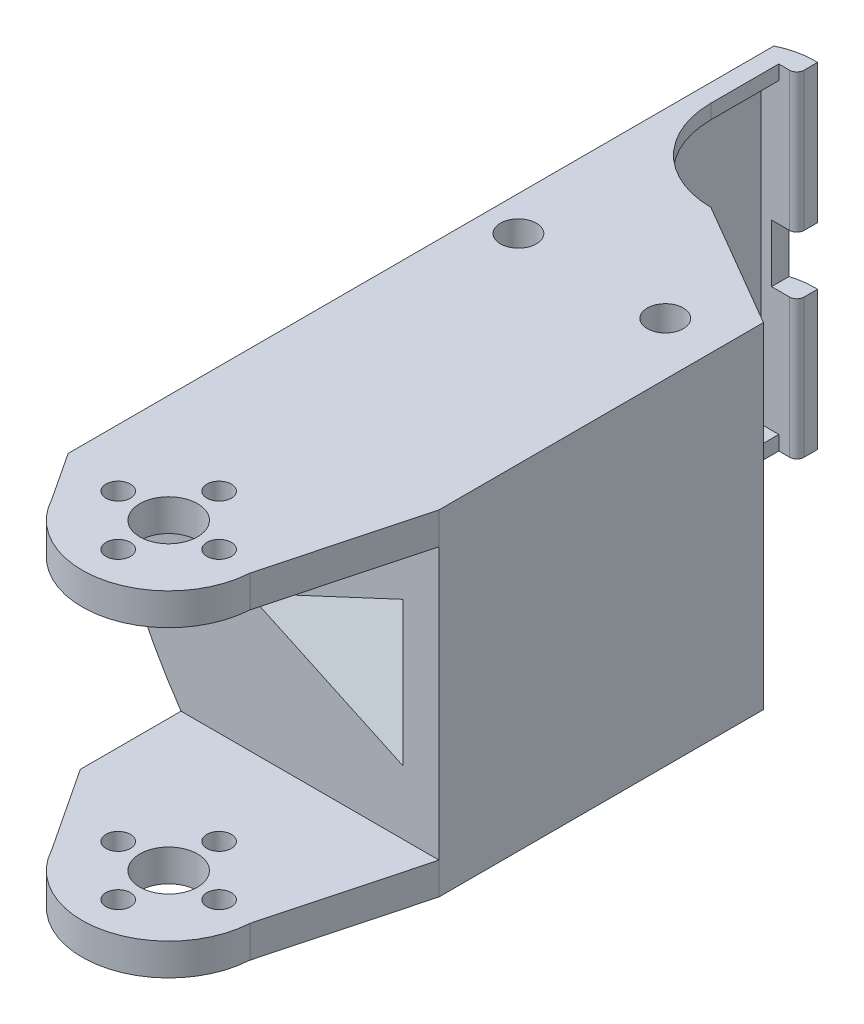
SolidWorks part; units mm, degrees
ref_plane "Front Plane" through (0, 0, 0) normal (0, 0, 1) x (1, 0, 0)
ref_plane "Top Plane" through (0, 0, 0) normal (0, 1, 0) x (1, 0, 0)
ref_plane "Right Plane" through (0, 0, 0) normal (1, 0, 0) x (0, 0, -1)
sketch "Sketch2" plane through (0, 0, 0) normal (0, 1, 0) x (1, 0, 0)
  line L0 (17.5, 0) -> (17.5, 37.7)
  line L1 (-15, 2.5) -> (15, 2.5)
  line L2 (-15, 2.5) -> (-15, 37.7)
  line L4 (15, 2.5) -> (15, 37.7)
  line L5 (17.5, 37.7) -> (15, 37.7)
  line L7 (-17.5, 37.7) -> (-17.5, 0)
  line L8 (-17.5, 0) -> (17.5, 0)
  line L10 (-17.5, 37.7) -> (-15, 37.7)
  point P4 (0, 2.5)
  point P12 (0, 0)
  dimension "D1" = 2.5
  dimension "D2" = 2.5
  dimension "D3" = 37.7
  dimension "D4" = 30
  dimension "D5" = 15
extrude "Boss-Extrude1" add sketch "Sketch2" along normal blind 32.5
sketch "Sketch4" plane through (0, 0, 0) normal (0, -1, 0) x (1, 0, 0)
  line L0 (-17.5, 0) -> (-17.5, -7.4438)
  line L8 (17.5, -7.4438) -> (17.5, 0)
  line L9 (17.5, 0) -> (-17.5, 0)
  line L10 (17.5, 0) -> (17.5, -37.7) construction
  line L13 (-17.5, -7.4438) -> (-17.5, -37.7)
  line L23 (-17.5, -37.7) -> (-15, -37.7)
  line L34 (-15, -37.7) -> (-15, -7.5)
  line L35 (-15, -2.5) -> (-15, -37.7) construction
  line L36 (-15, -7.5) -> (15, -7.5)
  line L37 (15, -37.7) -> (15, -2.5) construction
  line L38 (15, -7.5) -> (15, -37.7)
  line L39 (15, -37.7) -> (17.5, -37.7)
  line L40 (17.5, -37.7) -> (17.5, -7.4438)
  circle A2 centre (-10.1889, -4.95) radius 1.05
  circle A5 centre (10.1889, -4.95) radius 1.05
  dimension "D5" = 2.1
  dimension "D1" = 7.5
  dimension "D6" = 7.3111
  dimension "D7" = 4.95
  dimension "D8" = 7.3111
extrude "Boss-Extrude2" add sketch "Sketch4" along normal blind 2
sketch "Sketch7" plane through (0, -2, 0) normal (0, -1, 0) x (1, 0, 0)
  line L0 (-17.5, 0) -> (-17.5, -37.7)
  line L1 (-17.5, -37.7) -> (-15, -37.7)
  line L2 (-17.5, 0) -> (17.5, 0)
  line L4 (17.5, 0) -> (17.5, -37.7)
  line L5 (17.5, -37.7) -> (15, -37.7)
  line L6 (15, -37.7) -> (15, -7.5)
  line L7 (15, -7.5) -> (-15, -7.5)
  line L8 (-15, -7.5) -> (-15, -37.7)
  circle A2 centre (-10.1889, -4.95) radius 2.495
  circle A3 centre (10.1889, -4.95) radius 2.495
  dimension "D1" = 4.99
extrude "Wire spacing2" add sketch "Sketch7" along normal blind 3
sketch "Sketch8" plane through (0, -5, 0) normal (0, -1, 0) x (1, 0, 0)
  line L0 (-17.5, 0) -> (-17.5, -37.7)
  line L1 (-17.5, -37.7) -> (17.5, -37.7)
  line L2 (17.5, -37.7) -> (17.5, 0) construction
  line L3 (15, -37.7) -> (17.5, -37.7) construction
  line L4 (-17.5, 0) -> (17.5, 0)
  line L6 (17.5, 0) -> (17.5, -37.7)
  circle A0 centre (-10.1889, -4.95) radius 2.495
  circle A1 centre (10.1889, -4.95) radius 2.495
  circle A2 centre (10.1889, -4.95) radius 2.495 construction
  circle A3 centre (-10.1889, -4.95) radius 2.495 construction
extrude "Boss-Extrude6" add sketch "Sketch8" along normal blind 2
sketch "Sketch5" plane through (0, 32.5, 0) normal (0, 1, 0) x (1, 0, 0)
  line L0 (-7.439, 10) -> (-7.439, 2.5)
  line L9 (15, 2.5) -> (-15, 2.5) construction
  line L11 (-10.1889, 12) -> (-7.439, 10)
  line L13 (-17.5, 0) -> (17.5, 0) construction
  line L15 (-17.5, 0) -> (-17.5, 37.7)
  line L17 (10.1889, 12) -> (7.439, 10)
  line L20 (17.5, 0) -> (17.5, 37.7)
  line L21 (-7.439, 2.5) -> (7.439, 2.5)
  line L22 (7.439, 2.5) -> (7.439, 10)
  line L23 (-17.5, 0) -> (17.5, 0)
  line L24 (-10.1889, 12) -> (-15, 12)
  line L25 (-15, 37.7) -> (-15, 7.5) construction
  line L26 (-15, 12) -> (-15, 37.7)
  line L27 (-15, 37.7) -> (-17.5, 37.7)
  line L30 (17.5, 37.7) -> (15, 37.7)
  line L31 (15, 37.7) -> (15, 12)
  line L32 (15, 7.5) -> (15, 37.7) construction
  line L33 (15, 12) -> (10.1889, 12)
  circle A0 centre (-10.1889, 4.95) radius 1.05 construction
  circle A1 centre (-10.1889, 8.7) radius 1.05
  circle A2 centre (10.1889, 8.7) radius 1.05
  circle A3 centre (10.1889, 4.95) radius 1.05 construction
  dimension "D4" = 0
  dimension "D7" = 8.7
  dimension "D3" = 0
  dimension "D1" = 12
  dimension "D2" = 10.061
  dimension "D5" = 10
  dimension "D6" = 10.061
extrude "Boss-Extrude3" add sketch "Sketch5" along normal blind 2
sketch "Sketch9" plane through (0, 34.5, 0) normal (0, 1, 0) x (1, 0, 0)
  line L0 (-17.5, 0) -> (-17.5, 37.7)
  line L1 (-17.5, 37.7) -> (-15, 37.7)
  line L2 (-15, 37.7) -> (-15, 12)
  line L3 (-15, 12) -> (-10.1889, 12)
  line L4 (-10.1889, 12) -> (-7.439, 10)
  line L5 (-7.439, 10) -> (-7.439, 2.5)
  line L6 (-7.439, 2.5) -> (7.439, 2.5)
  line L7 (7.439, 2.5) -> (7.439, 10)
  line L8 (7.439, 10) -> (10.1889, 12)
  line L9 (10.1889, 12) -> (7.439, 10) construction
  line L10 (10.1889, 12) -> (15, 12)
  line L11 (15, 7.5) -> (15, 37.7) construction
  line L12 (15, 12) -> (15, 37.7)
  line L13 (15, 37.7) -> (17.5, 37.7)
  line L14 (17.5, 0) -> (17.5, 37.7) construction
  line L15 (17.5, 37.7) -> (15, 37.7) construction
  line L16 (17.5, 37.7) -> (17.5, 0)
  line L17 (17.5, 0) -> (-17.5, 0)
  line L18 (15, 12) -> (10.1889, 12) construction
  circle A0 centre (-10.1889, 8.7) radius 2.495
  circle A1 centre (10.1889, 8.7) radius 2.495
  point P10 (-10.1889, 12)
  point P38 (0, 0)
  dimension "D1" = 4.99
  dimension "D2" = 0
extrude "Wire spacing1" add sketch "Sketch9" along normal blind 3
sketch "Sketch10" plane through (0, 37.5, 0) normal (0, 1, 0) x (1, 0, 0)
  line L1 (-17.5, 37.7) -> (17.5, 37.7)
  line L2 (-17.5, 37.7) -> (-17.5, 0)
  line L3 (-17.5, 0) -> (17.5, 0)
  line L4 (17.5, 37.7) -> (17.5, 0)
  circle A0 centre (-10.1889, 8.7) radius 2.495
  circle A1 centre (10.1889, 8.7) radius 2.495
  circle A2 centre (-10.1889, 8.7) radius 2.495 construction
  circle A3 centre (10.1889, 8.7) radius 2.495 construction
extrude "Boss-Extrude8" add sketch "Sketch10" along normal blind 2
sketch "Sketch11" plane through (0, 39.5, 0) normal (0, 1, 0) x (1, 0, 0)
  line L0 (17.5, 37.7) -> (-17.5, 37.7) construction
  circle A0 centre (0, 37.7) radius 12.5
  dimension "D1" = 25
extrude "Cut-Extrude1" cut sketch "Sketch11" against normal through all
sketch "Sketch12" plane through (0, -7, 0) normal (0, -1, 0) x (1, 0, 0)
  line L4 (0, -25.2) -> (17.5, -15)
  line L5 (17.5, -37.7) -> (17.5, 0) construction
  line L6 (17.5, -15) -> (17.5, -47.4845)
  line L7 (17.5, -47.4845) -> (0, -25.2)
  line L8 (17.5, 0) -> (-17.5, 0) construction
  arc A1 (12.5, -37.7) -> (-12.5, -37.7) centre (0, -37.7) ccw construction
  dimension "D1" = 15
extrude "Cut-Extrude2" cut sketch "Sketch12" against normal through all
sketch "Sketch13" plane through (0, 0, 0) normal (0, 0, 1) x (1, 0, 0)
  line L0 (17.5, -7) -> (-17.5, -7) construction
  line L1 (17.5, 39.5) -> (-27.5, 39.5)
  line L2 (17.5, 39.5) -> (17.5, -7)
  line L3 (17.5, -7) -> (-27.5, -7)
  line L4 (-27.5, 39.5) -> (-27.5, -7)
  line L5 (-17.5, 39.5) -> (-17.5, -7) construction
  dimension "D1" = 10
extrude "Boss-Extrude9" add sketch "Sketch13" along normal blind 30
sketch "Sketch15" plane through (0, 0, 0) normal (0, 0, -1) x (-1, 0, 0)
  line L0 (17.5, -7) -> (12.5, -7) construction
  line L1 (27.5, 39.5) -> (15, 39.5)
  line L2 (27.5, 39.5) -> (27.5, -7)
  line L3 (27.5, -7) -> (15, -7)
  line L4 (15, 39.5) -> (15, -7)
extrude "Boss-Extrude10" add sketch "Sketch15" along normal blind 50
sketch "Sketch18" plane through (0, -7, 0) normal (0, -1, 0) x (1, 0, 0)
  line L0 (12.5, 35) -> (12.5, 30)
  line L1 (12.5, 30) -> (-12.5, 30)
  line L2 (-12.5, 35) -> (-12.5, 30)
  line L3 (12.5, 35) -> (9.3675, 42.5)
  line L4 (-9.3675, 42.5) -> (-12.5, 35)
  line L5 (-27.5, 30) -> (17.5, 30) construction
  circle A0 centre (0, 50) radius 4
  arc A1 (9.3675, 42.5) -> (-9.3675, 42.5) centre (0, 50) ccw
  circle A2 centre (0, 43) radius 1.7
  circle A3 centre (-7, 50) radius 1.7
  circle A4 centre (0, 57) radius 1.7
  circle A5 centre (7, 50) radius 1.7
  point P11 (7.7726, 26.3901)
  point P12 (0, 30)
  dimension "D3" = 8
  dimension "D5" = 12
  dimension "D7" = 3.4
  dimension "D1" = 25
  dimension "D2" = 20
  dimension "D4" = 5
  dimension "D6" = 12.5
  dimension "D8" = 7
  dimension "D9" = 7
  dimension "D10" = 7
  dimension "D11" = 7
  dimension "D12" = 0
  dimension "D13" = 0
extrude "Boss-Extrude11" add sketch "Sketch18" against normal up to surface (46.5 mm away) up to face at (-8.1361, 39.5, -19.1264)
sketch "Sketch22" plane through (0, -7, 0) normal (0, -1, 0) x (1, 0, 0)
  line L0 (-27.5, 30) -> (-9.3341, 57.5416)
  line L1 (-9.3341, 57.5416) -> (-9.3341, 30)
  line L2 (-9.3341, 30) -> (-27.5, 30)
  line L4 (17.5, 30) -> (10.749, 55.3347)
  line L5 (10.749, 55.3347) -> (7.9223, 30)
  line L6 (7.9223, 30) -> (17.5, 30)
  arc A0 (9.3675, 42.5) -> (-9.3675, 42.5) centre (0, 50) ccw construction
extrude "Boss-Extrude13" add sketch "Sketch22" against normal up to surface (46.5 mm away) up to face at (-4.6492, 39.5, 5.8206)
sketch "Sketch21" plane through (-27.5, 0, 0) normal (-1, 0, 0) x (0, 0, 1)
  line L1 (107.4125, 35.075) -> (30, 35.075)
  line L2 (107.4125, 35.075) -> (107.4125, -2.575)
  line L3 (107.4125, -2.575) -> (30, -2.575)
  line L4 (30, 35.075) -> (30, -2.575)
  line L6 (-50, -7) -> (-50, 39.5) construction
  line L7 (30, 39.5) -> (30, -7) construction
  point P6 (-50, 16.25)
  point P7 (30, 16.25)
  dimension "D1" = 37.65
  dimension "D2" = 0
extrude "Cut-Extrude3" cut sketch "Sketch21" against normal through all
sketch "Sketch26" plane through (0, 39.5, 0) normal (0, 1, 0) x (1, 0, 0)
  line L0 (-27.5, -30) -> (-27.5, 50) construction
  line L1 (-27.5, 29.3872) -> (-27.5, 50)
  line L2 (-27.5, 50) -> (-15, 50)
  spline S0 degree 2 poles (-15, 50) (-23.5947, 41.1535) (-27.5, 29.3872) knots 0 0 0 1 1 1
extrude "Cut-Extrude5" cut sketch "Sketch26" against normal through all
sketch "Sketch24" plane through (0, 0, 0) normal (0, 0, -1) x (-1, 0, 0)
  line L4 (15, -7) -> (27.5, -7)
  line L5 (27.5, -7) -> (27.5, 16.25)
  spline S0 degree 2 poles (27.5, 16.25) (23.3985, 3.4824) (15, -7) knots 0 0 0 1 1 1
extrude "Cut-Extrude4" cut sketch "Sketch24" against normal through all both and the other way through all
ref_plane "Plane1" through (0, 16.25, 0) normal (0, -1, 0) x (-1, 0, 0)
mirror "Mirror1" about plane through (0, 16.25, 0) normal (0, -1, 0) of "Cut-Extrude4"
sketch "Sketch27" plane through (0, 0, -2.5) normal (0, 0, -1) x (-1, 0, 0)
  line L0 (-12.5, 26.25) -> (8.9451, 16.25)
  line L1 (-24.75, 16.25) -> (24.75, 16.25) construction
  line L2 (8.9451, 16.25) -> (-12.5, 6.25)
  line L4 (-12.5, 6.25) -> (-12.5, 26.25)
  line L5 (-15, 32.5) -> (-15, 0) construction
  point P7 (-12.5, 16.25)
  dimension "D1" = 50
  dimension "D2" = 20
  dimension "D3" = 2.5
extrude "Cut-Extrude6" cut sketch "Sketch27" against normal through all
sketch "Sketch28" plane through (0, 39.5, 0) normal (0, 1, 0) x (1, 0, 0)
  line L0 (-15, 37.7) -> (-15, 50)
  line L1 (-15, 50) -> (-10, 50)
  line L2 (-10, 50) -> (-10, 47.127)
  line L3 (-10, 47.127) -> (-12.5, 47.127)
  line L4 (-12.5, 47.127) -> (-12.5, 37.7)
  line L5 (-15, 37.7) -> (-12.5, 37.7)
  dimension "D1" = 2.5
extrude "Boss-Extrude14" add sketch "Sketch28" against normal up to surface (46.5 mm away) up to face at (-0.858, -7, 10.1044)
fillet "Fillet2" radius 10 1 edges at (-15, 16.25, -50)
sketch "Sketch29" plane through (0, 0, -37.7) normal (0, 0, 1) x (1, 0, 0)
  line L1 (-15, 37.5) -> (-12.5, 37.5)
  line L2 (-15, 37.5) -> (-15, -5)
  line L3 (-15, -5) -> (-12.5, -5)
  line L4 (-12.5, 37.5) -> (-12.5, -5)
extrude "Cut-Extrude8" cut sketch "Sketch29" against normal up to surface (9.427 mm away) up to face at (-11.25, 16.25, -47.127)
fillet "Fillet3" radius 1 1 edges at (-10, 16.25, -47.127)
sketch "Sketch30" plane through (0, 0, -47.127) normal (0, 0, 1) x (1, 0, 0)
  line L0 (-24.75, 16.25) -> (24.75, 16.25) construction
  line L1 (-6.1884, 20.25) -> (-13.5, 20.25)
  line L2 (-6.1884, 20.25) -> (-6.1884, 12.25)
  line L3 (-6.1884, 12.25) -> (-13.5, 12.25)
  line L4 (-13.5, 20.25) -> (-13.5, 12.25)
  line L5 (-11, -7) -> (-11, 39.5) construction
  point P4 (-13.5, 16.25)
  dimension "D1" = 8
  dimension "D2" = 2.5
extrude "Cut-Extrude9" cut sketch "Sketch30" against normal blind 22.5
